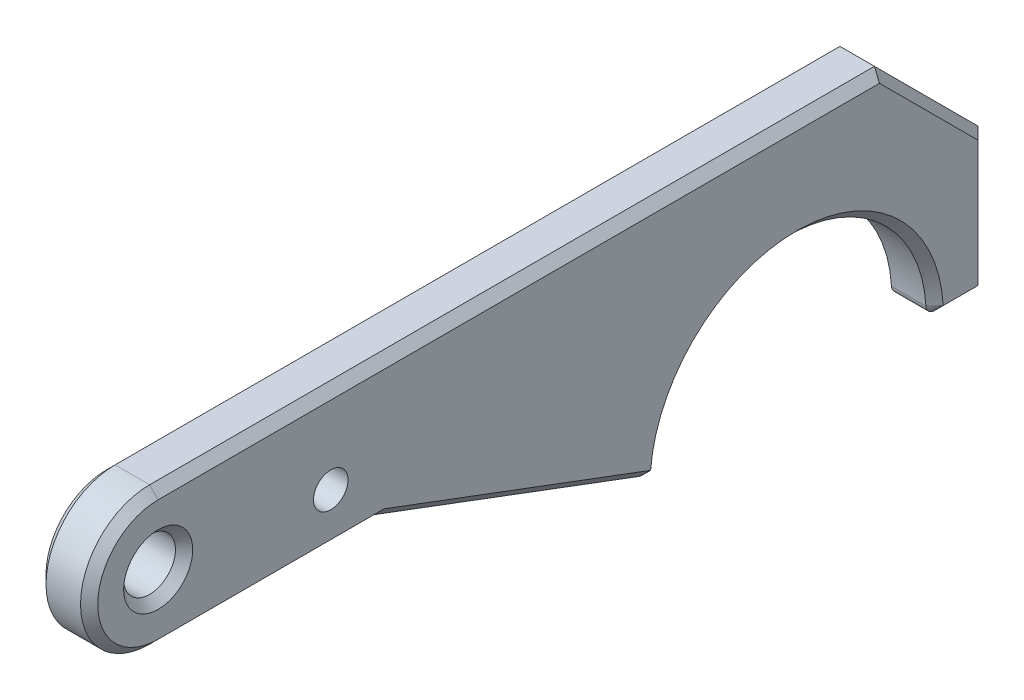
SolidWorks part; units mm, degrees
material "6061-T6 (SS)"
ref_plane "Front Plane" through (0, 0, 0) normal (0, 0, 1) x (1, 0, 0)
ref_plane "Top Plane" through (0, 0, 0) normal (0, 1, 0) x (1, 0, 0)
ref_plane "Right Plane" through (0, 0, 0) normal (1, 0, 0) x (0, 0, -1)
sketch "Sketch1" plane through (0, 0, 0) normal (1, 0, 0) x (0, 0, -1)
  line L0 (0, 12.7) -> (152.4, 12.7)
  line L1 (152.4, 12.7) -> (152.4, -31.75)
  line L2 (41.275, -12.7) -> (92.075, -31.75)
  line L3 (0, -12.7) -> (41.275, -12.7)
  line L4 (142.875, -31.75) -> (152.4, -31.75)
  circle A0 centre (0, 0) radius 4.7625
  circle A1 centre (0, 0) radius 12.7
  circle A2 centre (117.475, -31.75) radius 25.4
  dimension "D1" = 9.525
  dimension "D2" = 152.4
  dimension "D3" = 25.4
  dimension "D4" = 50.8
  dimension "D5" = 9.525
  dimension "D6" = 44.45
  dimension "D7" = 50.8
extrude "Boss-Extrude1" add sketch "Sketch1" along normal mid plane 9.525 contours A2 L4 L1 L0 A1 L3 L2 | A1 A0 region at (0, -3.1877, -82.9273) region at (0, 8.7263, -8.7263)
fillet "Fillet1" radius 1.5875 2 edges at (0, -31.75, -142.875) (0, -31.75, -92.075)
chamfer "Chamfer1" distance 19.05 angle 45 1 edges at (0, 12.7, -152.4)
chamfer "Chamfer2" distance 1.5875 angle 45 22 edges at (4.7625, 3.175, -142.875) (4.7625, -19.05, -152.4) (4.7625, -31.75, -148.4079) (4.7625, -31.3176, -143.3268) (4.7625, -6.352, -117.7901) (4.7625, -30.8361, -91.4308) (4.7625, -21.8405, -65.6497) (4.7625, -12.7, -20.6375) (4.7625, 0, 12.7) (4.7625, 12.7, -66.675) (-4.7625, 0, -4.7625) (-4.7625, 0, 12.7) (-4.7625, -12.7, -20.6375) (-4.7625, -21.8405, -65.6497) (-4.7625, -30.8361, -91.4308) (-4.7625, -6.352, -117.7901) (-4.7625, -31.3176, -143.3268) (-4.7625, -31.75, -148.4079) (-4.7625, -19.05, -152.4) (-4.7625, 3.175, -142.875) (-4.7625, 12.7, -66.675) (4.7625, 0, -4.7625)
ref_plane "Plane1" through (4.7625, -11.1125, 0) normal (0, 0, -1) x (-1, 0, 0)
sketch "Sketch3" plane through (4.7625, 0, 0) normal (1, 0, 0) x (0, 0, -1)
  circle A0 centre (31.75, -3.175) radius 3.175
  dimension "D1" = 6.35
  dimension "D2" = 31.75
  dimension "D3" = 3.175
extrude "Cut-Extrude1" cut sketch "Sketch3" against normal through all
